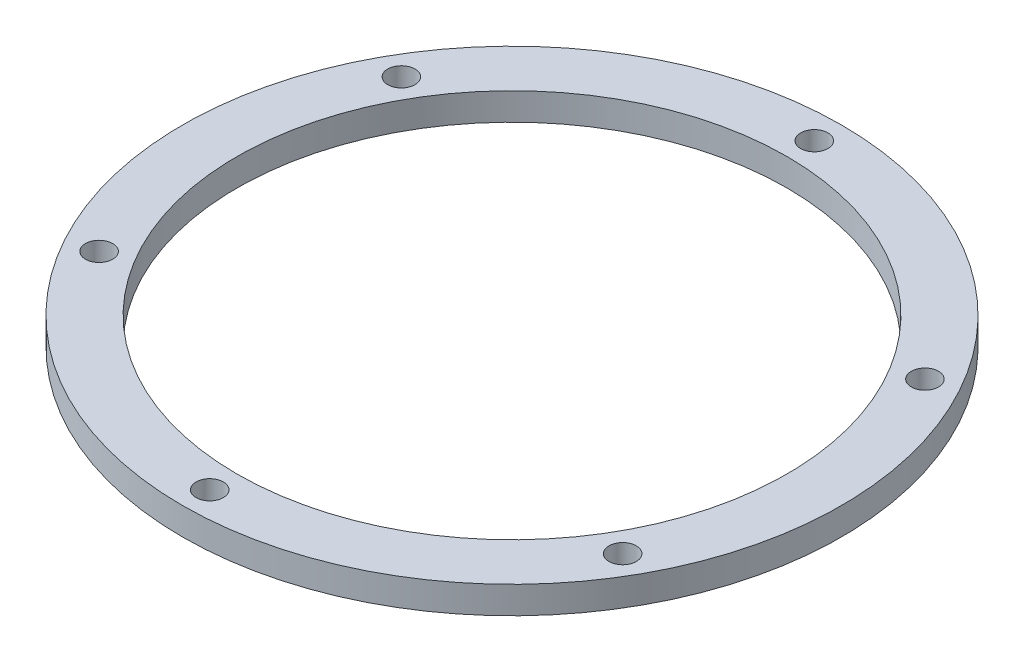
SolidWorks part; units mm, degrees
ref_plane "Front Plane" through (0, 0, 0) normal (0, 0, 1) x (1, 0, 0)
ref_plane "Top Plane" through (0, 0, 0) normal (0, 1, 0) x (1, 0, 0)
ref_plane "Right Plane" through (0, 0, 0) normal (1, 0, 0) x (0, 0, -1)
sketch "Sketch1" plane through (0, 0, 0) normal (0, 1, 0) x (1, 0, 0)
  circle A0 centre (0, 0) radius 30.25
  circle A1 centre (0, 0) radius 36.25
  dimension "D1" = 6
  dimension "D2" = 72.5
extrude "Boss-Extrude1" add sketch "Sketch1" along normal blind 3
sketch "Sketch2" plane through (0, 3, 0) normal (0, 1, 0) x (1, 0, 0)
  line L0 (0, 36.25) -> (0, 30.25) construction
  circle A0 centre (0, 0) radius 36.25 construction
  circle A1 centre (0, 0) radius 30.25 construction
  circle A2 centre (0, 33.25) radius 1.5
  dimension "D1" = 3
extrude "Cut-Extrude1" cut sketch "Sketch2" against normal through all both and the other way through all
pattern_circular "CirPattern1" count 6 every 60 about axis through (0, 3, 0) along (0, -1, 0) of "Cut-Extrude1"
